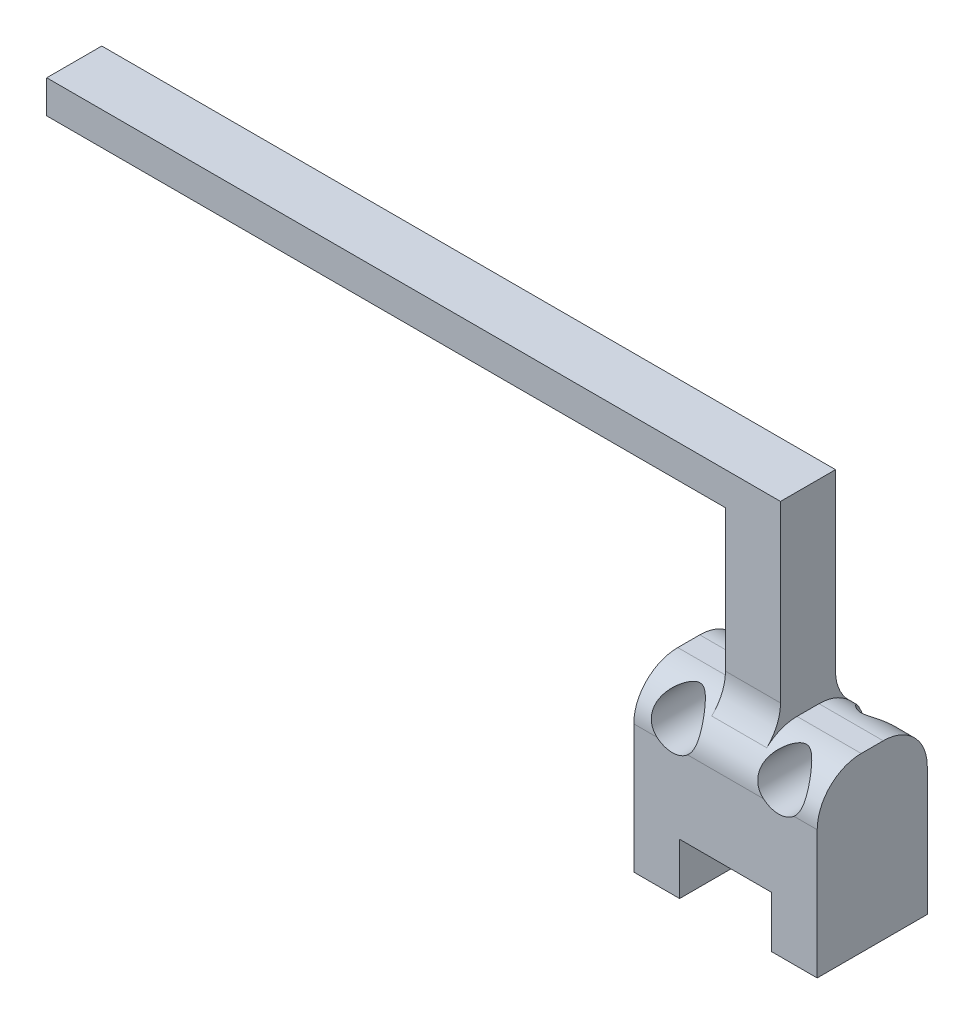
SolidWorks part; units mm, degrees
ref_plane "Front Plane" through (0, 0, 0) normal (0, 0, 1) x (1, 0, 0)
ref_plane "Top Plane" through (0, 0, 0) normal (0, 1, 0) x (1, 0, 0)
ref_plane "Right Plane" through (0, 0, 0) normal (1, 0, 0) x (0, 0, -1)
sketch "Sketch1" plane through (0, 0, 0) normal (0, 0, 1) x (1, 0, 0)
  line L19 (51.6669, -45.781) -> (59.1669, -45.781)
  line L20 (51.6669, -45.781) -> (41.6669, -45.781) construction
  line L21 (40.4169, -62.281) -> (52.9169, -62.281)
  line L22 (40.4169, -62.281) -> (40.4169, -69.281)
  line L24 (52.9169, -62.281) -> (52.9169, -69.281)
  line L25 (59.1669, -69.281) -> (34.1669, -69.281)
  line L28 (34.1669, -45.781) -> (41.6669, -45.781)
  line L32 (41.6669, -45.781) -> (51.6669, -45.781)
  line L33 (34.1669, -45.781) -> (34.1669, -69.281)
  line L34 (59.1669, -45.781) -> (59.1669, -69.281)
  line L35 (59.1669, -49.381) -> (34.1669, -49.381) construction
  line L36 (46.6669, -49.381) -> (46.6669, -45.781) construction
  circle A0 centre (53.9169, -49.381) radius 3.175
  circle A1 centre (39.4169, -49.381) radius 3.175
  point P0 (0, 0)
  point P9 (50, -65.781)
  point P11 (40.4169, -65.781)
  point P12 (46.6669, -47.581)
  dimension "D7" = 6.35
  dimension "D3" = 12.5
  dimension "D4" = 3.6
  dimension "D8" = 7.5
  dimension "D9" = 7.5
  dimension "D10" = 23.5
  dimension "D11" = 7
  dimension "D12" = 6.25
  dimension "D13" = 14.5
  dimension "D14" = 7.25
extrude "pusher base" add sketch "Sketch1" along normal blind 15 contours L32 L28 L19 A1 A0 L21 L24 L22 region at (46.6669, -57.06, 0)
sketch "Sketch3" plane through (0, -62.281, 0) normal (0, -1, 0) x (1, 0, 0)
  line L0 (46.6669, 15) -> (46.6669, 0) construction
  line L1 (40.4169, 15) -> (52.9169, 15) construction
  line L2 (40.4169, 0) -> (52.9169, 0) construction
  circle A0 centre (46.6669, 7.5) radius 1.95
  point P10 (46.6669, 7.5)
  dimension "D1" = 3.9
extrude "screw hole" cut sketch "Sketch3" against normal blind 7.5
ref_plane "Plane1" through (0, 0, 7.5) normal (0, 0, 1) x (1, 0, 0)
sketch "Sketch6" plane through (0, 0, 7.5) normal (0, 0, 1) x (1, 0, 0)
  line L0 (40.4169, -62.281) -> (52.9169, -62.281) construction
  line L5 (34.1669, -45.781) -> (59.1669, -45.781) construction
  line L6 (42.9169, -23.781) -> (50.4169, -23.781)
  line L11 (42.9169, -23.781) -> (42.9169, -45.781)
  line L12 (42.9169, -45.781) -> (50.4169, -45.781)
  line L13 (50.4169, -23.781) -> (50.4169, -45.781)
  line L14 (46.6669, -62.281) -> (46.6669, -29.281) construction
  line L15 (50.4169, -23.781) -> (42.9169, -23.781)
  line L16 (50.4169, -23.781) -> (50.4169, -19.281)
  line L17 (50.4169, -19.281) -> (42.9169, -19.281)
  line L18 (42.9169, -23.781) -> (42.9169, -19.281)
  point P2 (46.6669, -23.781)
  point P8 (46.6669, -45.781)
  dimension "D1" = 7.5
  dimension "D3" = 7.5
  dimension "D4" = 4.5
  dimension "D5" = 38.5
extrude "pusher head" add sketch "Sketch6" along normal mid plane 7.5 contours L18 L15 L6 L16 L17 | L13 L6 L12 | L11 L12 L6 region at (46.6669, -21.531, 7.5) region at (46.6669, -34.781, 7.5)
fillet "Fillet1" radius 6 2 edges at (46.6669, -45.781, 0) (46.6669, -45.781, 15)
fillet "Fillet5" radius 6 1 edges at (46.6669, -46.2189, 11.25)
fillet "Fillet6" radius 6 1 edges at (46.6669, -46.2189, 3.75)
sketch "Sketch8" plane through (0, 0, 3.75) normal (0, 0, -1) x (-1, 0, 0)
  line L0 (-42.9169, -43.0668) -> (-42.9169, -19.281) construction
  line L1 (-42.9169, -19.281) -> (49.5831, -19.281)
  line L2 (-42.9169, -19.281) -> (-42.9169, -23.781)
  line L3 (-42.9169, -23.781) -> (49.5831, -23.781)
  line L4 (49.5831, -19.281) -> (49.5831, -23.781)
  point P5 (0, 0)
  dimension "D1" = 92.5
  dimension "D2" = 4.5
extrude "Boss-Extrude1" add sketch "Sketch8" against normal blind 7.5
equation "\"PusherHeight\"=2"
equation "\"PusherWidth\"=11"
equation "\"PusherLongWidth\"=5"
equation "\"RodDiameter\"=0.5"
equation "\"HookLength\"=2.01152"
equation "\"HookHeight\"=0.999652"
equation "\"HookInnerLength\"=2"
equation "\"RodHeightDistance\"=0.4276"
equation "\"RodWidthDistance\"=0.75"
equation "\"PusherDepth\"=2"
equation "\"BuckleShaftDiameter\"=0.383646"
equation "\"BeltBuckleDistance\"=1.5"
equation "\"DowelDiameter\"=0.635"
equation "\"D7@Sketch1\"=\"DowelDiameter\""
equation "\"RodSeperationDistance\"=3.98"
equation "\"BuckleNutDiameter\"=0.39"
equation "\"D1@Sketch3\"=\"BuckleNutDiameter\""
equation "\"belt hole width\"=1.4"
equation "\"pusher height\"=3.5175"
equation "\"pusher slot width\"=0.75"
equation "\"D1@Sketch6\"=\"pusher slot width\""
equation "\"pushing bar width\"=0.45"
equation "\"D4@Sketch6\"=\"pushing bar width\""
equation "\"doweltotop\"=0.36"
equation "\"D4@Sketch1\"=\"doweltotop\""
equation "\"dowel separation\"=1.45"
equation "\"D13@Sketch1\"=\"dowel separation\""
